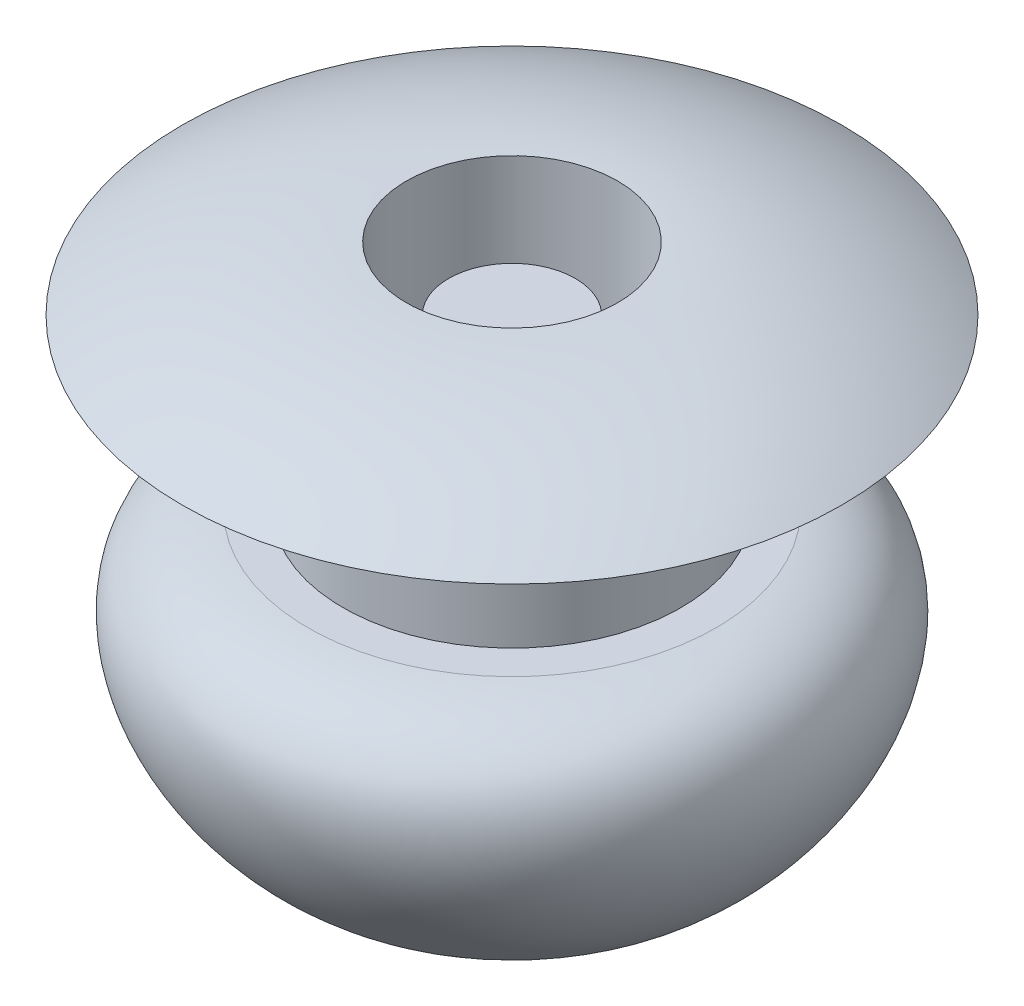
SolidWorks part; units mm, degrees
material "AISI 316 Stal nierdzewna odprężona (SS)"
ref_plane "Płaszczyzna przednia" through (0, 0, 0) normal (0, 0, 1) x (1, 0, 0)
ref_plane "Płaszczyzna górna" through (0, 0, 0) normal (0, 1, 0) x (1, 0, 0)
ref_plane "Płaszczyzna prawa" through (0, 0, 0) normal (1, 0, 0) x (0, 0, -1)
sketch "Szkic1" plane through (0, 0, 0) normal (1, 0, 0) x (0, 0, -1)
  line L0 (0, 0) -> (0, -2)
  line L1 (0, 0) -> (-0.75, 0)
  line L2 (-0.75, 0) -> (-0.75, -2)
  line L3 (-0.75, -2) -> (-1.25, -2)
  line L4 (-1.25, -2) -> (-1.25, 0.75)
  line L5 (-3.9, 0) -> (-2, 0)
  line L6 (-2, 0) -> (-2, -2)
  line L7 (-2, -2) -> (-2.4139, -2)
  line L8 (0, 0) -> (0, 0.4842) construction
  line L10 (0, -2) -> (0, -3.5)
  line L11 (-573, -2) -> (7, -2) construction
  arc A0 (-1.25, 0.75) -> (-3.9, 0) centre (-1.25, -4.3067) ccw
  ellipse E0 centre (0, -2.75) end of major axis (-1.75, -2.75) minor radius 0.75 (-0.956, -3.3782) -> (0, -3.5) ccw
  spline S0 degree 3 poles (-2.4139, -2) (-3.8586, -2.1633) (-3.5584, -4.323) (-0.9713, -5.8719) (-0.3411, -3.792) (-0.956, -3.3782) knots 0 0 0 0 0.454219 0.705201 1 1 1 1
  point P25 (-2.2069, -2)
  dimension "D1" = 7.8
  dimension "D2" = 2.5
  dimension "D3" = 4
  dimension "D4" = 0.75
  dimension "D5" = 1.5
  dimension "D6" = 1.5
  dimension "D7" = 3.5
  dimension "D8" = 3.1855
  dimension "D9" = 2.5026
  dimension "D10" = 1.9
  dimension "D11" = 1.3782
  dimension "D12" = 0.5792
  dimension "D13" = 4.8278
  dimension "D14" = 3.3858
  dimension "D15" = 2.8395
  dimension "D16" = 1.25
  dimension "D17" = 0.6409
  dimension "D18" = 0.956
revolve "Obrót1" add sketch "Szkic1" angle 360 about L8
